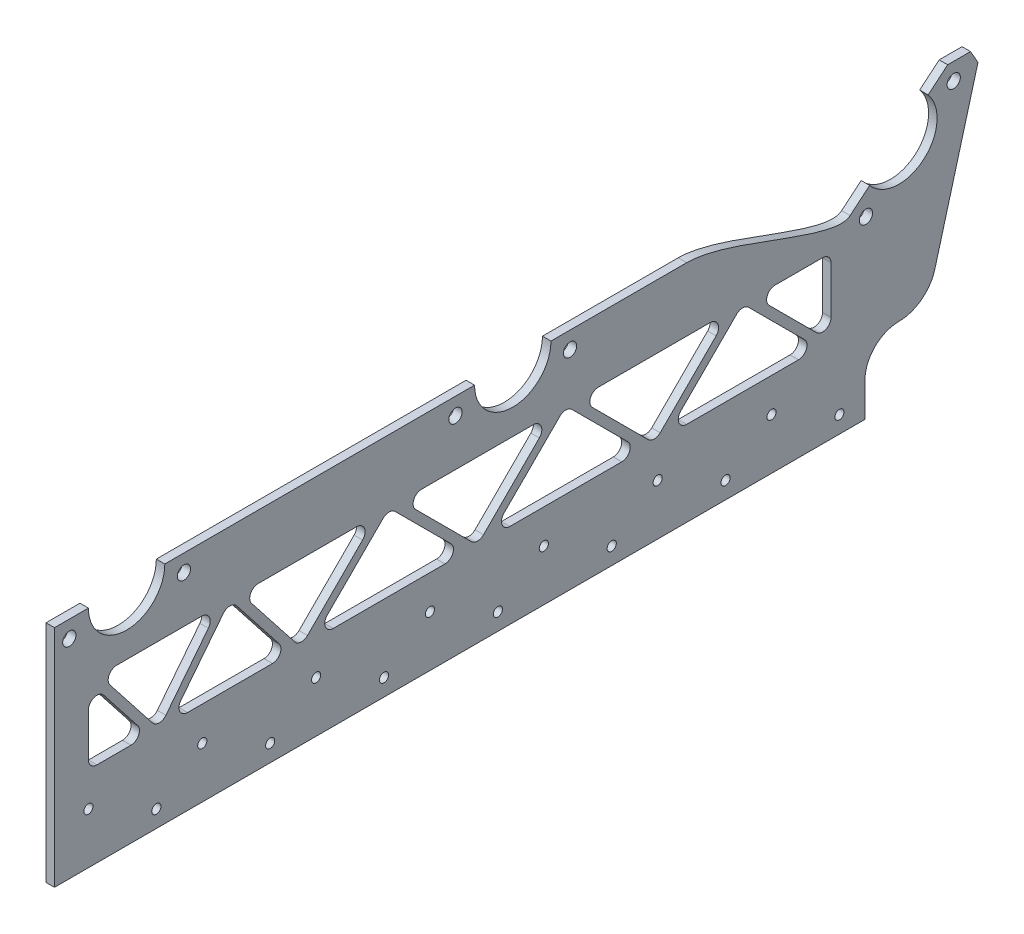
SolidWorks part; units mm, degrees
material "6061 Alloy"
ref_plane "Front Plane" through (0, 0, 0) normal (0, 0, 1) x (1, 0, 0)
ref_plane "Top Plane" through (0, 0, 0) normal (0, 1, 0) x (1, 0, 0)
ref_plane "Right Plane" through (0, 0, 0) normal (1, 0, 0) x (0, 0, -1)
sketch "Sketch1" plane through (0, 0, 0) normal (1, 0, 0) x (0, 0, -1)
  line L0 (-12.7, -12.7) -> (-315.9125, -12.7)
  line L1 (-315.9125, -12.7) -> (-315.9125, 71.4375)
  line L2 (-315.9125, 71.4375) -> (-303.2125, 71.4375)
  line L3 (-274.6375, 71.4375) -> (-158.75, 71.4375)
  line L5 (10.9449, 80.6213) -> (18.2432, 86.7453)
  line L7 (-315.9125, 12.7) -> (13.4735, 12.7) construction
  line L8 (-12.7, -12.7) -> (-12.7, 0)
  line L9 (0, 12.4079) -> (0, 12.7) construction
  line L10 (13.4735, 22.9788) -> (30.9432, 86.7453)
  line L12 (-10.9449, 62.2537) -> (10.9449, 80.6213) construction
  line L13 (18.2432, 86.7453) -> (30.9432, 86.7453)
  line L14 (-130.175, 71.4375) -> (-79.375, 71.4375)
  line L15 (-10.9449, 62.2537) -> (-18.2432, 56.1297)
  line L16 (-315.9125, 15.875) -> (13.4735, 15.875) construction
  line L17 (-288.925, 71.4375) -> (-144.4625, 71.4375) construction
  line L18 (0, 71.4375) -> (-144.4625, 71.4375) construction
  arc A3 (0, 12.7) -> (13.4735, 22.9788) centre (0, 26.67) ccw
  arc A4 (0, 12.7) -> (-12.7, 0) centre (0, 0) ccw
  circle A5 centre (0, 0) radius 12.4079 construction
  arc A6 (-303.2125, 71.4375) -> (-274.6375, 71.4375) centre (-288.925, 71.4375) ccw
  arc A7 (-158.75, 71.4375) -> (-130.175, 71.4375) centre (-144.4625, 71.4375) ccw
  arc A8 (-10.9449, 62.2537) -> (10.9449, 80.6213) centre (0, 71.4375) ccw
  spline S0 degree 3 poles (-18.2432, 56.1297) (-24.729, 50.6874) (-62.4417, 71.4375) (-79.375, 71.4375) knots 0 0 0 0 1 1 1 1
  point P4 (-164.3062, -12.7)
  dimension "D1" = 25.4
  dimension "D3" = 12.7
  dimension "D5" = 28.575
  dimension "D6" = 41.275
  dimension "D7" = 13.97
  dimension "D8" = 12.7
  dimension "D10" = 24.8158
  dimension "D13" = 9.5273
  dimension "D14" = 140
  dimension "D15" = 50.8
  dimension "D16" = 50.8
  dimension "D17" = 25.4
  dimension "D2" = 0
  dimension "D4" = 12.7
  dimension "D9" = 12.7
  dimension "D11" = 288.925
  dimension "D12" = 288.925
  dimension "D18" = 3.175
extrude "Boss-Extrude1" add sketch "Sketch1" along normal blind 3.175
hole_wizard "#10 Clearance Hole1" positions "Sketch2" profile "Sketch3" hole size "#10" standard "ANSI Inch" end condition through all
sketch "Sketch2" plane through (3.175, 0, 0) normal (1, 0, 0) x (0, 0, -1)
  line L0 (-310.3562, 65.0875) -> (-267.4937, 65.0875) construction
  line L2 (-165.8938, 65.0875) -> (-123.0312, 65.0875) construction
  line L4 (-12.3356, 52.7974) -> (20.499, 80.3489) construction
  line L6 (-303.2125, 71.4375) -> (-315.9125, 71.4375) construction
  line L7 (-288.925, 65.0875) -> (-288.925, 71.4375) construction
  line L9 (-144.4625, 71.4375) -> (-144.4625, 65.0875) construction
  line L11 (0, 71.4375) -> (4.0817, 66.5731) construction
  line L14 (18.2432, 86.7453) -> (10.9449, 80.6213) construction
  line L15 (18.2432, 86.7453) -> (10.9449, 80.6213) construction
  point P0 (-310.3562, 65.0875)
  point P2 (-267.4937, 65.0875)
  point P4 (-165.8938, 65.0875)
  point P6 (-123.0312, 65.0875)
  point P8 (-12.3356, 52.7974)
  point P10 (20.499, 80.3489)
  dimension "D1" = 42.8625
  dimension "D2" = 6.35
  dimension "D3" = 6.35
sketch "Sketch3" plane through (3.175, 65.0875, 310.3562) normal (0, 1, 0) x (0, 0, -1)
  line L0 (0, 0) -> (0, 3.175)
  line L1 (0, 3.175) -> (2.4892, 3.175)
  line L2 (2.4892, 3.175) -> (2.4892, 0)
  line L5 (2.4892, 0) -> (0, 0)
  line L11 (0, -6.35) -> (0, 107.95) construction
  dimension "Thru Hole Dia." = 4.9784
  dimension "Thru Hole Depth" = 3.175
chamfer "Chamfer1" distance 5.08 angle 45 1 edges at (1.5875, 86.7453, -30.9432) first distance on face at (1.5875, 54.862, -22.2083)
hole_wizard "1/8 (0.135) Diameter Hole1" positions "Sketch4" profile "Sketch5" hole size "1/8" standard "ANSI Inch"
sketch "Sketch4" plane through (3.175, 0, 0) normal (1, 0, 0) x (0, 0, -1)
  line L0 (-315.9125, -12.7) -> (-12.7, -12.7) construction
  line L1 (-12.7, -12.7) -> (-12.7, 0) construction
  line L2 (-315.9125, 71.4375) -> (-315.9125, -12.7) construction
  point P0 (-22.2504, -6.35)
  point P2 (-47.6504, 6.35)
  point P14 (-64.8441, -6.35)
  point P15 (-90.2441, 6.35)
  point P16 (-107.4378, -6.35)
  point P17 (-132.8378, 6.35)
  point P18 (-150.0314, -6.35)
  point P19 (-175.4315, 6.35)
  point P20 (-192.6251, -6.35)
  point P21 (-218.0251, 6.35)
  point P22 (-235.2188, -6.35)
  point P23 (-260.6188, 6.35)
  point P24 (-277.8125, -6.35)
  point P25 (-303.2125, 6.35)
  dimension "D1" = 6.35
  dimension "D2" = 9.5504
  dimension "D3" = 12.7
  dimension "D4" = 25.4
  dimension "D6" = 12.7
  dimension "D5" = 7
sketch "Sketch5" plane through (3.175, -6.35, 22.2504) normal (0, 1, 0) x (0, 0, -1)
  line L0 (0, 0) -> (0, 17.5402)
  line L1 (0, 17.5402) -> (1.7145, 16.51)
  line L2 (1.7145, 16.51) -> (1.7145, 0)
  line L5 (1.7145, 0) -> (0, 0)
  line L10 (0, 17.5402) -> (-1.7145, 16.51) construction
  line L11 (0, -6.35) -> (0, 107.95) construction
  dimension "Hole Dia." = 3.429
  dimension "Hole Depth" = 16.51
  dimension "Drill Angle" = 118
sketch "Sketch6" plane through (3.175, 0, 0) normal (1, 0, 0) x (0, 0, -1)
  line L0 (-303.2125, 47.625) -> (-303.2125, 19.05)
  line L1 (-303.2125, 19.05) -> (-280.7754, 19.05)
  line L2 (-280.7754, 19.05) -> (-303.2125, 47.625)
  line L3 (-315.9125, 12.7) -> (-12.7, 12.7) construction
  line L4 (-315.9125, 71.4375) -> (-315.9125, -12.7) construction
  line L5 (-315.9125, -12.7) -> (-12.7, -12.7) construction
  line L6 (-315.9125, 15.875) -> (-12.7, 15.875) construction
  line L7 (-299.1757, 47.625) -> (-276.7386, 19.05)
  line L8 (-276.7386, 19.05) -> (-254.3015, 47.625)
  line L9 (-254.3015, 47.625) -> (-299.1757, 47.625)
  line L10 (-272.7018, 19.05) -> (-250.2647, 47.625)
  line L11 (-250.2647, 47.625) -> (-227.8276, 19.05)
  line L12 (-227.8276, 19.05) -> (-272.7018, 19.05)
  line L13 (-246.2279, 47.625) -> (-223.7908, 19.05)
  line L14 (-223.7908, 19.05) -> (-195.2158, 47.625)
  line L15 (-195.2158, 47.625) -> (-246.2279, 47.625)
  line L16 (-219.3006, 19.05) -> (-190.7256, 47.625)
  line L17 (-190.7256, 47.625) -> (-162.1506, 19.05)
  line L18 (-162.1506, 19.05) -> (-219.3006, 19.05)
  line L19 (-186.2355, 47.625) -> (-157.6605, 19.05)
  line L20 (-157.6605, 19.05) -> (-129.0855, 47.625)
  line L21 (-129.0855, 47.625) -> (-186.2355, 47.625)
  line L22 (-124.5954, 47.625) -> (-153.1704, 19.05)
  line L23 (-153.1704, 19.05) -> (-96.0204, 19.05)
  line L24 (-96.0204, 19.05) -> (-124.5954, 47.625)
  line L25 (-120.1053, 47.625) -> (-91.5303, 19.05)
  line L26 (-91.5303, 19.05) -> (-62.9553, 47.625)
  line L27 (-62.9553, 47.625) -> (-120.1053, 47.625)
  line L28 (-58.4651, 47.625) -> (-87.0401, 19.05)
  line L29 (-87.0401, 19.05) -> (-29.8901, 19.05)
  line L30 (-29.8901, 19.05) -> (-58.4651, 47.625)
  line L31 (-12.7, -12.7) -> (-12.7, 0) construction
  line L32 (-53.975, 47.625) -> (-25.4, 19.05)
  line L33 (-25.4, 19.05) -> (-25.4, 47.625)
  line L34 (-25.4, 47.625) -> (-53.975, 47.625)
  arc A0 (-303.2125, 71.4375) -> (-274.6375, 71.4375) centre (-288.925, 71.4375) ccw construction
  point P34 (0, 0)
  point P39 (-27.2303, 19.05)
  point P40 (-48.6312, 49.32)
  point P41 (0, 0)
  point P42 (-222.5929, 19.05)
  point P43 (0, 0)
  point P46 (-40.4994, 50.3955)
  point P47 (-42.3684, 50.3955)
  point P48 (0, 0)
  point P49 (-102.8294, 49.0698)
  point P50 (-181.5326, 49.0698)
  point P51 (0, 0)
  point P52 (0, 0)
  dimension "D15" = 9.525
  dimension "D1" = 25.4
  dimension "D3" = 3.175
  dimension "D4" = 12.7
  dimension "D5" = 3.175
  dimension "D6" = 3.175
  dimension "D7" = 3.175
  dimension "D8" = 3.175
  dimension "D9" = 3.175
  dimension "D10" = 3.175
  dimension "D11" = 3.175
  dimension "D12" = 3.175
  dimension "D13" = 3.175
  dimension "D14" = 12.7
  dimension "D2" = 3.175
extrude "Cut-Extrude1" cut sketch "Sketch6" against normal through all
fillet "Fillet1" radius 3.175 30 edges at (1.5875, 19.05, 25.4) (1.5875, 47.625, 53.975) (1.5875, 47.625, 25.4) (1.5875, 19.05, 162.1506) (1.5875, 19.05, 219.3006) (1.5875, 19.05, 91.5303) (1.5875, 47.625, 120.1053) (1.5875, 47.625, 62.9553) (1.5875, 19.05, 87.0401) (1.5875, 47.625, 58.4651) (1.5875, 19.05, 29.8901) (1.5875, 19.05, 157.6605) (1.5875, 47.625, 186.2355) (1.5875, 47.625, 129.0855) (1.5875, 19.05, 153.1704) (1.5875, 47.625, 124.5954) (1.5875, 19.05, 96.0204) (1.5875, 47.625, 190.7256) (1.5875, 19.05, 223.7908) (1.5875, 47.625, 246.2279) (1.5875, 47.625, 195.2158) (1.5875, 19.05, 227.8276) (1.5875, 19.05, 272.7018) (1.5875, 47.625, 250.2647) (1.5875, 19.05, 276.7386) (1.5875, 47.625, 299.1757) (1.5875, 47.625, 254.3015) (1.5875, 19.05, 303.2125) (1.5875, 19.05, 280.7754) (1.5875, 47.625, 303.2125)
